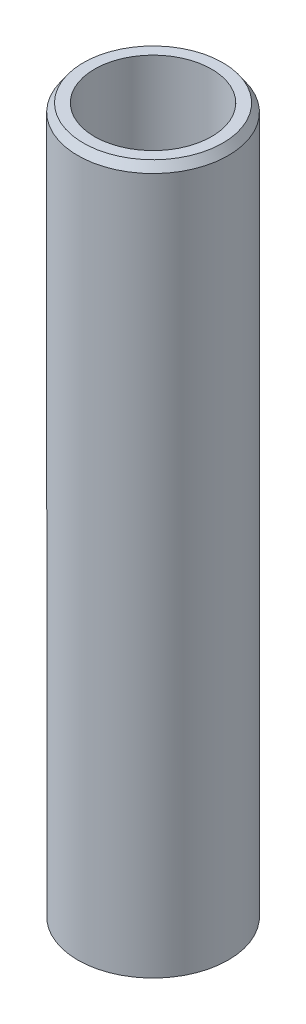
SolidWorks part; units mm, degrees
ref_plane "Front Plane" through (0, 0, 0) normal (0, 0, 1) x (1, 0, 0)
ref_plane "Top Plane" through (0, 0, 0) normal (0, 1, 0) x (1, 0, 0)
ref_plane "Right Plane" through (0, 0, 0) normal (1, 0, 0) x (0, 0, -1)
sketch "Sketch1" plane through (0, 0, 0) normal (0, 1, 0) x (1, 0, 0)
  circle A0 centre (0, 0) radius 47.5
  dimension "SHAFT_OD" = 95
extrude "Boss-Extrude1" add sketch "Sketch1" along normal blind 448.4477
sketch "Sketch2" plane through (0, 0, 0) normal (0, 1, 0) x (1, 0, 0)
  circle A0 centre (0, 0) radius 36.9462
  dimension "BORE_D" = 73.8925
extrude "Cut-Extrude1" cut sketch "Sketch2" along normal through all
chamfer "Chamfer1" distance 5.0789 angle 34.498 2 edges at (0, 448.4477, 47.5) (0, 0, 47.5) first distance on face at (0, 448.4477, 47.5) first distance on face at (0, 0, 36.9462)
